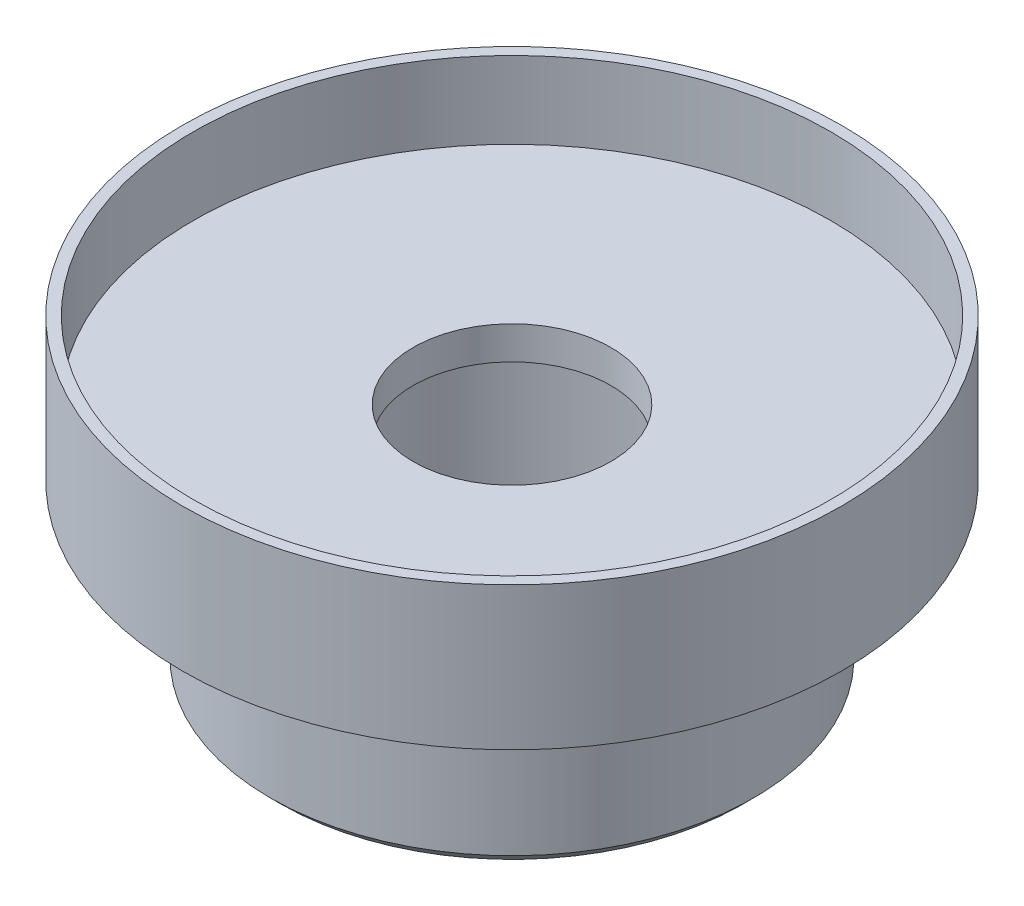
SolidWorks part; units mm, degrees
material "Alliage de zinc AC41A, brut"
ref_plane "Plan de face" through (0, 0, 0) normal (0, 0, 1) x (1, 0, 0)
ref_plane "Plan de dessus" through (0, 0, 0) normal (0, 1, 0) x (1, 0, 0)
ref_plane "Plan de droite" through (0, 0, 0) normal (1, 0, 0) x (0, 0, -1)
sketch "Esquisse1" plane through (0, 0, 0) normal (0, 1, 0) x (1, 0, 0)
  circle A0 centre (0, 0) radius 11
  dimension "D1" = 22
extrude "Boss.-Extru.1" add sketch "Esquisse1" along normal blind 7.5
sketch "Esquisse3" plane through (0, 7.5, 0) normal (0, 1, 0) x (1, 0, 0)
  circle A0 centre (0, 0) radius 15
  dimension "D1" = 30
extrude "Boss.-Extru.2" add sketch "Esquisse3" along normal blind 6.5
chamfer "Chanfrein1" distance 0.5 angle 45 1 edges at (0, 0, 11)
chamfer "Chanfrein2" distance 1 angle 45 1 edges at (0, 7.5, 11)
sketch "Esquisse4" plane through (0, 14, 0) normal (0, 1, 0) x (1, 0, 0)
  circle A0 centre (0, 0) radius 14.5
  dimension "D1" = 29
extrude "Enlèv. mat.-Extru.1" cut sketch "Esquisse4" against normal blind 3.5
sketch "Esquisse5" plane through (0, 10.5, 0) normal (0, 1, 0) x (1, 0, 0)
  circle A0 centre (0, 0) radius 4.5
  dimension "D1" = 9
extrude "Enlèv. mat.-Extru.2" cut sketch "Esquisse5" against normal blind 1.5 contours A0
sketch "Esquisse6" plane through (0, 9, 0) normal (0, 1, 0) x (1, 0, 0)
  circle A0 centre (0, 0) radius 7
  dimension "D1" = 14
extrude "Enlèv. mat.-Extru.3" cut sketch "Esquisse6" against normal blind 1
sketch "Esquisse20" plane through (0, 8, 0) normal (0, 1, 0) x (1, 0, 0)
  circle A0 centre (0, 0) radius 8
  dimension "D1" = 16
extrude "Enlèv. mat.-Extru.4" cut sketch "Esquisse20" against normal blind 8
cosmetic thread "Représentation de filetage1" parameters "D1"=4, "D2"=17
